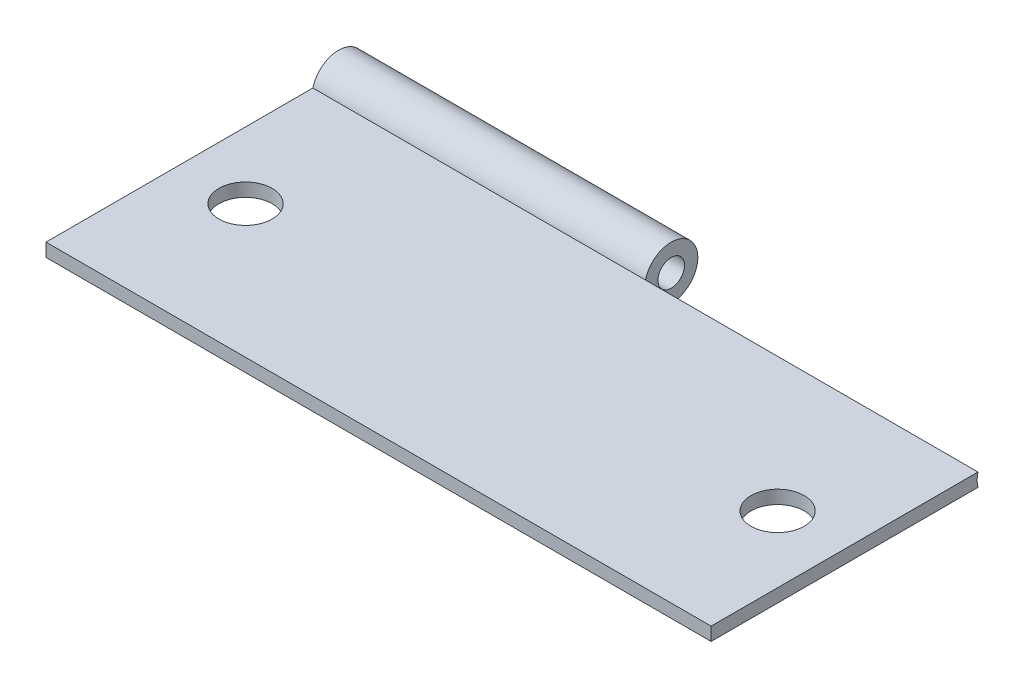
SolidWorks part; units mm, degrees
ref_plane "Front Plane" through (0, 0, 0) normal (0, 0, 1) x (1, 0, 0)
ref_plane "Top Plane" through (0, 0, 0) normal (0, 1, 0) x (1, 0, 0)
ref_plane "Right Plane" through (0, 0, 0) normal (1, 0, 0) x (0, 0, -1)
sketch "Sketch1" plane through (0, 0, 0) normal (0, 1, 0) x (1, 0, 0)
  line L1 (25, 10) -> (-25, 10)
  line L2 (25, 10) -> (25, -10)
  line L3 (25, -10) -> (-25, -10)
  line L4 (-25, 10) -> (-25, -10)
  line L5 (25, 10) -> (-25, -10) construction
  line L6 (25, -10) -> (-25, 10) construction
  point P0 (0, 0)
  dimension "D1" = 50
  dimension "D2" = 20
extrude "Boss-Extrude1" add sketch "Sketch1" along normal mid plane 1
sketch "Sketch3" plane through (-25, 0, 0) normal (-1, 0, 0) x (0, 0, 1)
  circle A0 centre (-12, 0) radius 2
  dimension "D2" = 4
  dimension "D1" = 12
extrude "Boss-Extrude2" add sketch "Sketch3" against normal blind 25 separate body
sketch "Sketch4" plane through (0, 0, 0) normal (1, 0, 0) x (0, 0, -1)
  circle A0 centre (12, 0) radius 1
  dimension "D1" = 2
extrude "Cut-Extrude1" cut sketch "Sketch4" against normal blind 20
sketch "Sketch5" plane through (0, 0, -10) normal (0, 0, -1) x (-1, 0, 0)
  line L4 (-25, -0.5) -> (25, -0.5)
  line L5 (25, -0.5) -> (25, 0.5)
  line L6 (25, 0.5) -> (-25, 0.5)
  line L7 (-25, 0.5) -> (-25, -0.5)
  line L8 (-25, -0.5) -> (25, -0.5)
  line L9 (25, -0.5) -> (25, 0.5)
  line L10 (25, 0.5) -> (-25, 0.5)
  line L11 (-25, 0.5) -> (-25, -0.5)
  dimension "D1" = 0
extrude "Boss-Extrude3" add sketch "Sketch5" along normal up to surface up to face at (0, 0, -10)
sketch "Sketch6" plane through (0, 0.5, 0) normal (0, 1, 0) x (1, 0, 0)
  line L0 (0, 0) -> (0, -10) construction
  line L1 (-25, -10) -> (25, -10) construction
  circle A0 centre (-20, 0) radius 2
  circle A1 centre (20, 0) radius 2
  dimension "D1" = 4
  dimension "D2" = 20
extrude "Cut-Extrude2" cut sketch "Sketch6" against normal blind 20
